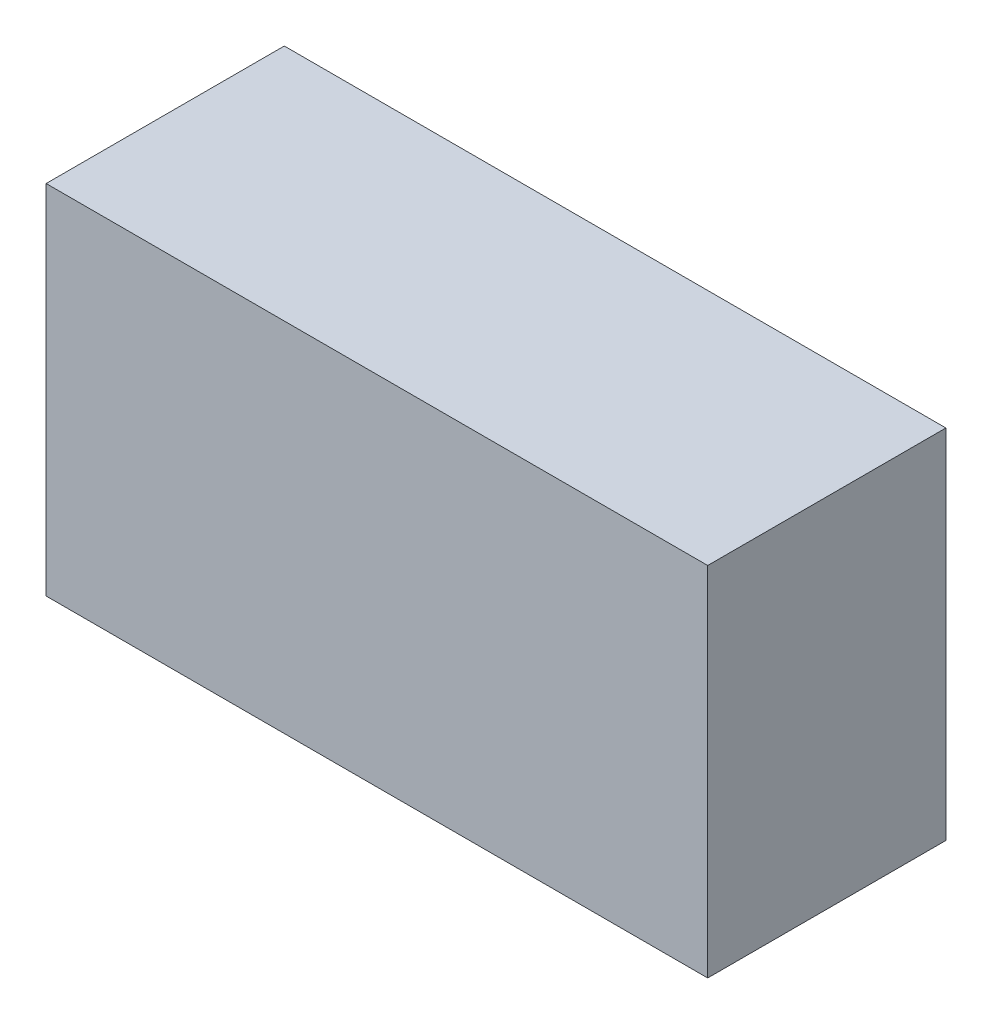
SolidWorks part; units mm, degrees
ref_plane "Front Plane" through (0, 0, 0) normal (0, 0, 1) x (1, 0, 0)
ref_plane "Top Plane" through (0, 0, 0) normal (0, 1, 0) x (1, 0, 0)
ref_plane "Right Plane" through (0, 0, 0) normal (1, 0, 0) x (0, 0, -1)
sketch "Sketch1" plane through (0, 0, 0) normal (0, 0, 1) x (1, 0, 0)
  line L1 (-50, 27) -> (0, 27)
  line L2 (-50, 27) -> (-50, 0)
  line L3 (-50, 0) -> (0, 0)
  line L4 (0, 27) -> (0, 0)
  dimension "D1" = 50
  dimension "D2" = 27
extrude "Boss-Extrude1" add sketch "Sketch1" along normal blind 18
sketch "Sketch2" plane through (-50, 0, 0) normal (-1, 0, 0) x (0, 0, 1)
  line L4 (18, 27) -> (0, 27) construction
  line L5 (18, 27) -> (18, 0) construction
  line L6 (18, 0) -> (0, 0) construction
  circle A0 centre (9, 20.25) radius 3
  circle A1 centre (9, 6.75) radius 3
  point P8 (9, 0)
  dimension "D3" = 6
  dimension "D4" = 6
  dimension "D1" = 6.75
  dimension "D2" = 9
  dimension "D5" = 6.75
extrude "Boss-Extrude3" add sketch "Sketch2" along normal blind 2
fillet "Fillet1" radius 1 1 edges at (-52, 17.25, 9)
sketch "Sketch3" plane through (-52, 0, 0) normal (-1, 0, 0) x (0, 0, 1)
  circle A0 centre (9, 6.75) radius 2.25
  dimension "D1" = 4.5
extrude "Cut-Extrude1" cut sketch "Sketch3" against normal blind 2
fillet "Fillet3" radius 1 1 edges at (-52, 4.5, 9)
